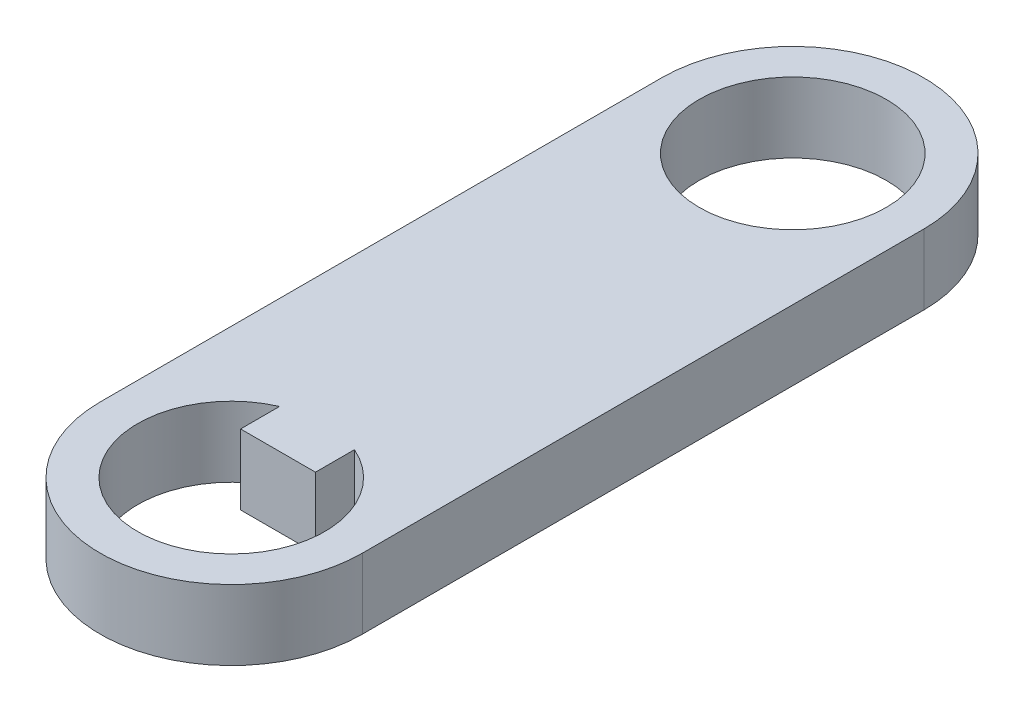
SolidWorks part; units mm, degrees
ref_plane "Front Plane" through (0, 0, 0) normal (0, 0, 1) x (1, 0, 0)
ref_plane "Top Plane" through (0, 0, 0) normal (0, 1, 0) x (1, 0, 0)
ref_plane "Right Plane" through (0, 0, 0) normal (1, 0, 0) x (0, 0, -1)
sketch "Sketch1" plane through (0, 0, 0) normal (0, 1, 0) x (1, 0, 0)
  line L0 (0, 60) -> (0, 0) construction
  line L1 (14, 60) -> (14, 0)
  line L2 (-14, 60) -> (-14, 0)
  line L4 (4, 5) -> (-4, 5)
  line L5 (4, 5) -> (4, 15)
  line L6 (4, 15) -> (-4, 15)
  line L7 (-4, 5) -> (-4, 15)
  line L8 (4, 5) -> (-4, 15) construction
  line L9 (4, 15) -> (-4, 5) construction
  arc A0 (14, 60) -> (-14, 60) centre (0, 60) ccw
  arc A1 (-14, 0) -> (14, 0) centre (0, 0) ccw
  circle A2 centre (0, 0) radius 10
  circle A3 centre (0, 60) radius 10
  point P2 (0, 30)
  point P9 (0, 10)
  dimension "D1" = 20
  dimension "D2" = 20
  dimension "D4" = 14
  dimension "D3" = 60
  dimension "D5" = 8
  dimension "D6" = 10
extrude "Boss-Extrude1" add sketch "Sketch1" along normal blind 7.5 contours L2 A1 L1 A0 A3 A2 L7 L6 L5 | L5 L4 L7 L6 region at (0, 0, -30.458)
equation "\"shaftDiam\" = 20mm"
equation "\"keyW\" = 8mm"
equation "\"keyL\" = 10mm"
equation "\"clearance\" = .8mm"
equation "\"handleShaftLen\" = 60mm"
equation "\"D1@Sketch1\"=\"shaftDiam\""
equation "\"D2@Sketch1\"=\"shaftDiam\""
equation "\"D3@Sketch1\"=\"handleShaftLen\""
equation "\"D4@Sketch1\"=\"shaftDiam\"*.7"
equation "\"D5@Sketch1\"=\"keyW\""
equation "\"D6@Sketch1\"=\"keyL\""
equation "\"D1@Boss-Extrude1\"=\"handleShaftLen\"/8"
